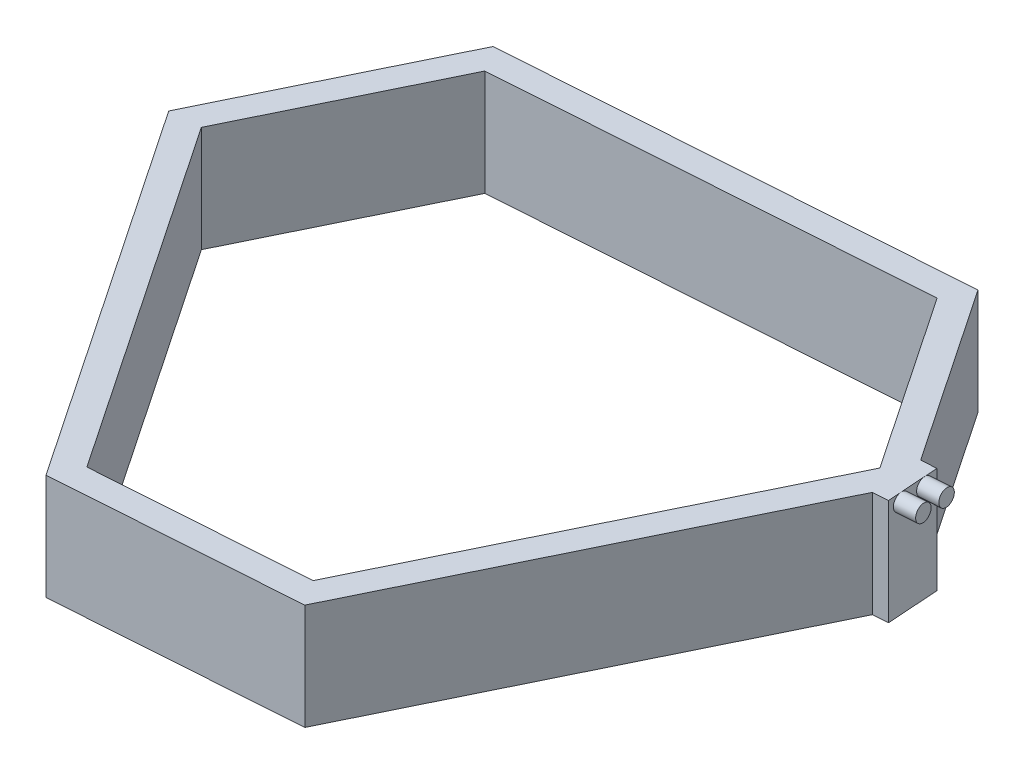
SolidWorks part; units mm, degrees
ref_plane "Front Plane" through (0, 0, 0) normal (0, 0, 1) x (1, 0, 0)
ref_plane "Top Plane" through (0, 0, 0) normal (0, 1, 0) x (1, 0, 0)
ref_plane "Right Plane" through (0, 0, 0) normal (1, 0, 0) x (0, 0, -1)
sketch "Sketch1" plane through (0, 0, 0) normal (0, 1, 0) x (1, 0, 0)
  line L0 (28.4005, -42.1195) -> (-28.4005, 42.1195)
  line L1 (-28.4005, 42.1195) -> (-6.1242, 87.7748)
  line L11 (-6.1242, 87.7748) -> (95.2294, 94.8464)
  line L12 (79.0773, -38.5837) -> (123.6299, 52.7269)
  line L13 (123.6299, 52.7269) -> (95.2294, 94.8464)
  line L14 (79.0773, -38.5837) -> (28.4005, -42.1195)
  line L15 (83.1766, -44.6631) -> (25.1852, -48.7093)
  line L16 (25.1852, -48.7093) -> (-35.7151, 41.6091)
  line L17 (-35.7151, 41.6091) -> (-10.2235, 93.8542)
  line L18 (-10.2235, 93.8542) -> (98.4447, 101.4362)
  line L19 (130.9445, 53.2373) -> (98.4447, 101.4362)
  line L20 (83.1766, -44.6631) -> (130.9445, 53.2373)
  point P4 (0, 0)
  dimension "D1" = 101.6
  dimension "D2" = 6.35
  dimension "D3" = 120
  dimension "D5" = 50.8
  dimension "D6" = 101.6
extrude "Boss-Extrude1" add sketch "Sketch1" along normal blind 25.4
sketch "Sketch2" plane through (0, 25.4, 0) normal (0, 1, 0) x (1, 0, 0)
  line L0 (123.1938, 58.9769) -> (124.0638, 46.5073)
  line L1 (130.5419, 59.4896) -> (131.412, 47.02)
  line L15 (123.1938, 58.9769) -> (130.5419, 59.4896)
  line L16 (131.412, 47.02) -> (124.0638, 46.5073)
  point P4 (123.6299, 52.7269)
  point P7 (123.6299, 52.7269)
  point P10 (123.6299, 52.7269)
  dimension "D1" = 12.5
extrude "Boss-Extrude2" add sketch "Sketch2" against normal up to surface (25.4 mm away) up to face at (48.6354, 0, -32.7941)
sketch "Sketch3" plane through (134.0401, 0, -9.3522) normal (0.9976, 0, -0.0696) x (-0.0696, 0, -0.9976)
  circle A0 centre (41.0093, 23.4) radius 2
  circle A1 centre (47.0093, 23.4) radius 2
  point P3 (44.0093, 25.4)
extrude "Boss-Extrude3" add sketch "Sketch3" along normal blind 5 contours A0 | A1
